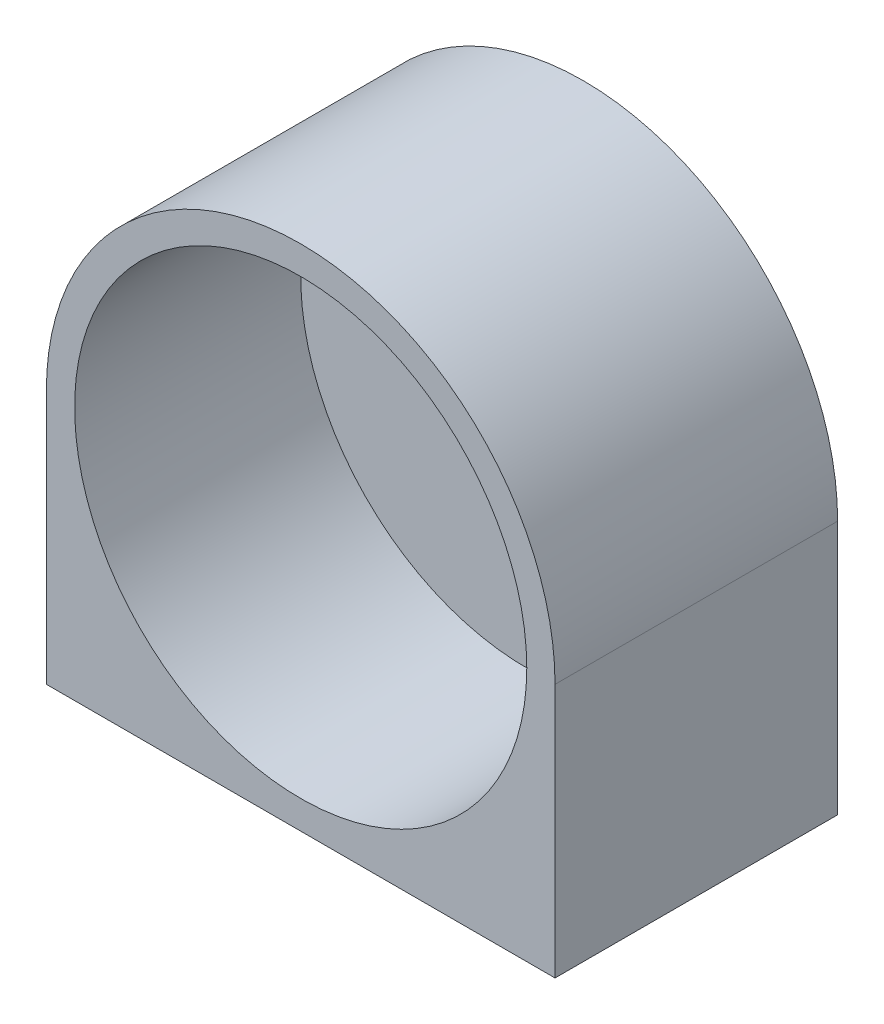
SolidWorks part; units mm, degrees
ref_plane "Front Plane" through (0, 0, 0) normal (0, 0, 1) x (1, 0, 0)
ref_plane "Top Plane" through (0, 0, 0) normal (0, 1, 0) x (1, 0, 0)
ref_plane "Right Plane" through (0, 0, 0) normal (1, 0, 0) x (0, 0, -1)
sketch "Sketch2" plane through (0, 0, 0) normal (0, 0, 1) x (1, 0, 0)
  circle A1 centre (0, 0) radius 22.5
  dimension "D2" = 45
extrude "Boss-Extrude3" add sketch "Sketch2" along normal blind 25
sketch "Sketch6" plane through (0, 0, 0) normal (0, 0, 1) x (1, 0, 0)
  line L1 (-22.5, 0) -> (22.5, 0)
  line L2 (-22.5, 0) -> (-22.5, -22.5)
  line L3 (-22.5, -22.5) -> (22.5, -22.5)
  line L4 (22.5, 0) -> (22.5, -22.5)
  circle A0 centre (0, 0) radius 22.5 construction
extrude "Boss-Extrude4" add sketch "Sketch6" along normal blind 25
sketch "Sketch4" plane through (0, 0, 25) normal (0, 0, 1) x (1, 0, 0)
  circle A0 centre (0, 0) radius 20
  dimension "D1" = 40
extrude "Cut-Extrude1" cut sketch "Sketch4" against normal blind 20
sketch "Sketch5" plane through (0, 0, 0) normal (0, 0, -1) x (-1, 0, 0)
  circle A0 centre (0, 0) radius 2.5
  dimension "D1" = 5
extrude "Cut-Extrude2" cut sketch "Sketch5" against normal up to surface (5 mm away) up to face at (20, 0, 5)
